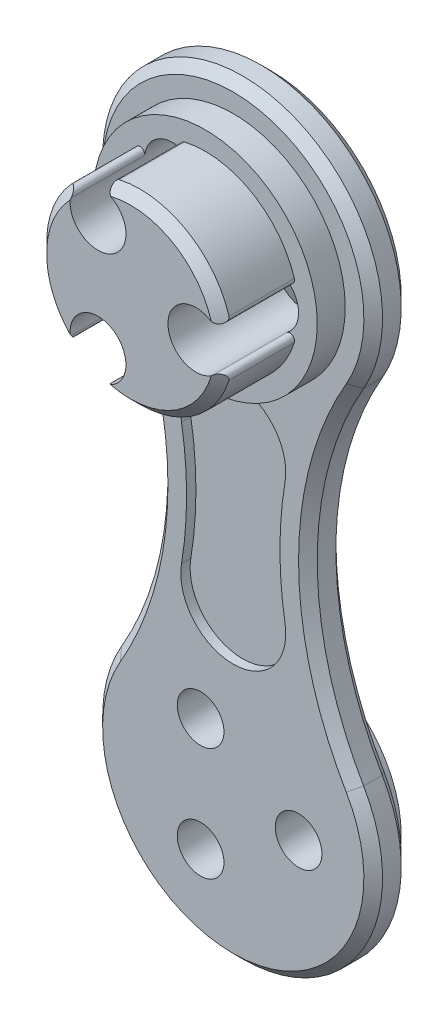
SolidWorks part; units mm, degrees
material "A2017"
ref_plane "正面" through (0, 0, 0) normal (0, 0, 1) x (1, 0, 0)
ref_plane "平面" through (0, 0, 0) normal (0, 1, 0) x (1, 0, 0)
ref_plane "右側面" through (0, 0, 0) normal (1, 0, 0) x (0, 0, -1)
sketch "ｽｹｯﾁ1" plane through (0, 0, 0) normal (0, 0, 1) x (1, 0, 0)
  line L0 (0, 12.9904) -> (0, 0) construction
  line L1 (0, 0) -> (0, -12.9904) construction
  line L2 (0, 0) -> (50000, 0) construction
  arc A0 (6.4848, 9.2225) -> (-6.4848, 9.2225) centre (0, 12.9904) ccw
  arc A1 (-6.4848, -9.2225) -> (6.4848, -9.2225) centre (0, -12.9904) ccw
  arc A2 (-6.4848, 9.2225) -> (-6.4848, -9.2225) centre (-22.3571, 0) cw
  arc A3 (6.4848, 9.2225) -> (6.4848, -9.2225) centre (22.3571, 0) ccw
  point P14 (-4, 0)
  point P15 (4, 0)
  dimension "D2" = 15
  dimension "D1" = 25.9808
  dimension "D3" = 8
extrude "ﾎﾞｽ - 押し出し1" add sketch "ｽｹｯﾁ1" along normal mid plane 2
sketch "ｽｹｯﾁ2" plane through (0, 0, 1) normal (0, 0, 1) x (1, 0, 0)
  circle A0 centre (0, 12.9904) radius 6
  dimension "D1" = 12
extrude "ﾎﾞｽ - 押し出し2" add sketch "ｽｹｯﾁ2" along normal blind 1.5
sketch "ｽｹｯﾁ3" plane through (0, 0, -1) normal (0, 0, -1) x (-1, 0, 0)
  circle A0 centre (0, -12.9904) radius 7.5
  arc A3 (-6.4848, -9.2225) -> (6.4848, -9.2225) centre (0, -12.9904) ccw construction
extrude "ﾎﾞｽ - 押し出し3" add sketch "ｽｹｯﾁ3" along normal blind 1
sketch "ｽｹｯﾁ4" plane through (0, 0, 2.5) normal (0, 0, 1) x (1, 0, 0)
  circle A0 centre (0, 12.9904) radius 5
  dimension "D1" = 10
extrude "ﾎﾞｽ - 押し出し4" add sketch "ｽｹｯﾁ4" along normal blind 4
sketch "ｽｹｯﾁ10" plane through (0, 0, 6.5) normal (0, 0, 1) x (1, 0, 0)
  line L0 (-1.75, 16.0215) -> (-3.75, 19.4856) construction
  line L1 (-4, 0) -> (4, 0) construction
  line L2 (-1.75, -16.0215) -> (-3.75, -19.4856) construction
  arc A0 (-3.241, 16.1857) -> (-1.1468, 17.3948) centre (-1.75, 16.0215) ccw
  circle A1 centre (0, 12.9904) radius 5 construction
  arc A2 (4.3878, 14.1995) -> (4.3878, 11.7813) centre (3.5, 12.9904) ccw
  arc A3 (-1.1468, 8.5859) -> (-3.241, 9.795) centre (-1.75, 9.9593) ccw
  arc A4 (6.4848, 9.2225) -> (-6.4848, 9.2225) centre (0, 12.9904) ccw construction
  circle A6 centre (0, 12.9904) radius 5 construction
  arc A7 (-3.241, 16.1857) -> (-3.6731, 16.3827) centre (-3.4895, 16.2131) ccw
  arc A9 (-1.1468, 17.3948) -> (-1.1013, 17.8676) centre (-1.0462, 17.6237) cw
  arc A10 (4.3878, 11.7813) -> (4.7744, 11.5055) centre (4.5357, 11.5798) cw
  arc A11 (4.3878, 14.1995) -> (4.7744, 14.4752) centre (4.5357, 14.401) ccw
  arc A12 (-3.241, 9.795) -> (-3.6731, 9.598) centre (-3.4895, 9.7676) cw
  arc A13 (-1.1468, 8.5859) -> (-1.1013, 8.1132) centre (-1.0462, 8.357) ccw
  arc A16 (-1.1013, 17.8676) -> (-3.6731, 16.3827) centre (0, 12.9904) ccw
  arc A17 (4.7744, 11.5055) -> (4.7744, 14.4752) centre (0, 12.9904) ccw
  arc A18 (-3.6731, 9.598) -> (-1.1013, 8.1132) centre (0, 12.9904) ccw
  arc A19 (-6.4848, -9.2225) -> (-6.4848, 9.2225) centre (-22.3571, 0) ccw construction
  arc A20 (6.4848, 9.2225) -> (6.4848, -9.2225) centre (22.3571, 0) ccw construction
  arc A21 (-3.6731, -9.598) -> (-1.1013, -8.1132) centre (0, -12.9904) cw
  arc A22 (4.7744, -11.5055) -> (4.7744, -14.4752) centre (0, -12.9904) cw
  arc A23 (-1.1013, -17.8676) -> (-3.6731, -16.3827) centre (0, -12.9904) cw
  arc A26 (-1.1468, -8.5859) -> (-1.1013, -8.1132) centre (-1.0462, -8.357) cw
  arc A27 (-3.241, -9.795) -> (-3.6731, -9.598) centre (-3.4895, -9.7676) ccw
  arc A28 (4.3878, -14.1995) -> (4.7744, -14.4752) centre (4.5357, -14.401) cw
  arc A29 (4.3878, -11.7813) -> (4.7744, -11.5055) centre (4.5357, -11.5798) ccw
  arc A30 (-1.1468, -17.3948) -> (-1.1013, -17.8676) centre (-1.0462, -17.6237) ccw
  arc A31 (-3.241, -16.1857) -> (-3.6731, -16.3827) centre (-3.4895, -16.2131) cw
  arc A34 (-1.1468, -8.5859) -> (-3.241, -9.795) centre (-1.75, -9.9593) cw
  arc A35 (4.3878, -14.1995) -> (4.3878, -11.7813) centre (3.5, -12.9904) cw
  arc A36 (-3.241, -16.1857) -> (-1.1468, -17.3948) centre (-1.75, -16.0215) cw
  point P13 (0, 12.9904)
  point P45 (0, 12.9904)
  dimension "D2" = 3
  dimension "D3" = 0.5
  dimension "D1" = 3
  dimension "D4" = 3
extrude "ｶｯﾄ - 押し出し2" cut sketch "ｽｹｯﾁ10" against normal through all
sketch "ｽｹｯﾁ13" plane through (0, 0, 2.5) normal (0, 0, 1) x (1, 0, 0)
  circle A0 centre (0, 12.9904) radius 6 construction
  circle A1 centre (0, 12.9904) radius 6
extrude "ﾎﾞｽ - 押し出し7" add sketch "ｽｹｯﾁ13" against normal up to surface (3.5 mm away) up to face at (-2.0452, 9.448, -1)
sketch "ｽｹｯﾁ14" plane through (0, 0, -2) normal (0, 0, -1) x (-1, 0, 0)
  arc A0 (6.4848, -9.2225) -> (-6.4848, -9.2225) centre (0, -12.9904) ccw construction
  circle A1 centre (0, -12.9904) radius 7.5
  arc A2 (1.1468, -8.5859) -> (3.241, -9.795) centre (1.75, -9.9593) ccw construction
  arc A4 (3.241, -16.1857) -> (1.1468, -17.3948) centre (1.75, -16.0215) ccw construction
  arc A5 (-4.3878, -14.1995) -> (-4.3878, -11.7813) centre (-3.5, -12.9904) ccw construction
  circle A6 centre (1.75, -9.9593) radius 1.5
  circle A8 centre (1.75, -16.0215) radius 1.5
  circle A9 centre (-3.5, -12.9904) radius 1.5
extrude "ﾎﾞｽ - 押し出し8" add sketch "ｽｹｯﾁ14" against normal up to surface (3 mm away) up to face at (-2.0452, -16.5328, 1)
sketch "ｽｹｯﾁ18" plane through (0, 0, 2.5) normal (0, 0, 1) x (1, 0, 0)
  arc A0 (4.3878, 14.1995) -> (4.3878, 11.7813) centre (3.5, 12.9904) ccw construction
  arc A1 (-3.241, 16.1857) -> (-1.1468, 17.3948) centre (-1.75, 16.0215) ccw construction
  arc A2 (-1.1468, 8.5859) -> (-3.241, 9.795) centre (-1.75, 9.9593) ccw construction
  circle A4 centre (3.5, 12.9904) radius 1.5
  circle A5 centre (-1.75, 16.0215) radius 1.5
  circle A6 centre (-1.75, 9.9593) radius 1.5
extrude "ｶｯﾄ - 押し出し3" cut sketch "ｽｹｯﾁ18" against normal through all
sketch "ｽｹｯﾁ19" plane through (0, 0, -2) normal (0, 0, -1) x (-1, 0, 0)
  circle A0 centre (1.75, -9.9593) radius 1
  circle A1 centre (1.75, -16.0215) radius 1
  circle A3 centre (-3.5, -12.9904) radius 1
  circle A4 centre (1.75, -9.9593) radius 1.5 construction
  circle A5 centre (1.75, -9.9593) radius 1.5
  circle A7 centre (1.75, -16.0215) radius 1.5 construction
  circle A8 centre (-3.5, -12.9904) radius 1.5 construction
  circle A10 centre (1.75, -16.0215) radius 1.5
  circle A11 centre (-3.5, -12.9904) radius 1.5
  dimension "D1" = 2
extrude "ﾎﾞｽ - 押し出し9" add sketch "ｽｹｯﾁ19" against normal up to surface (3 mm away)
hole_wizard "M3x0.5 ねじ穴1" positions "ｽｹｯﾁ21" profile "ｽｹｯﾁ20" tap size "M3x0.5" standard "Jis" end condition through all
sketch "ｽｹｯﾁ21" plane through (0, 0, 1) normal (0, 0, 1) x (1, 0, 0)
  point P0 (-1.75, -9.9593)
  point P6 (-1.75, -16.0215)
  point P9 (3.5, -12.9904)
sketch "ｽｹｯﾁ20" plane through (-1.75, -9.9593, 1) normal (1, 0, 0) x (0, -1, 0)
  line L0 (0, 0) -> (0, 3)
  line L1 (0, 3) -> (1.25, 3)
  line L2 (1.25, 3) -> (1.25, 0)
  line L5 (1.25, 0) -> (0, 0)
  line L11 (0, -6.35) -> (0, 107.95) construction
  dimension "次ｻｰﾌｪｽまでのねじ下穴ﾄﾞﾘﾙ直径" = 2.5
  dimension "次ｻｰﾌｪｽまでのねじ下穴ﾄﾞﾘﾙの深さ" = 3
cosmetic thread "穴のねじ山1" parameters "D2"=3
cosmetic thread "穴のねじ山2" parameters "D2"=3
cosmetic thread "穴のねじ山4" parameters "D2"=3
sketch "ｽｹｯﾁ22" plane through (0, 0, -2) normal (0, 0, -1) x (-1, 0, 0)
  circle A0 centre (0, -12.9904) radius 6
  circle A1 centre (0, -12.9904) radius 7.5 construction
  circle A2 centre (0, -12.9904) radius 7.5
  dimension "D1" = 12
extrude "ｶｯﾄ - 押し出し4" cut sketch "ｽｹｯﾁ22" against normal up to surface (1 mm away) up to face at (-3.25, 9.9593, -1)
chamfer "面取り1" distance 1.7 angle 45 3 edges at (-3.25, 16.0215, -1) (-3.25, 9.9593, -1) (2, 12.9904, -1)
chamfer "面取り2" distance 0.5 angle 45 19 edges at (4, 0, 1) (0, 20.4904, 1) (-5, 12.9904, 6.5) (-3.3858, 16.4406, 6.5) (-1.2951, 17.6477, 6.5) (-4, 0, 1) (0, 20.4904, -1) (2.5, 17.3205, 6.5) (4.6809, 14.1974, 6.5) (4.6809, 11.7833, 6.5) (2.5, 8.6603, 6.5) (0, -20.4904, 1) (-1.2951, 8.3331, 6.5) (-3.3858, 9.5402, 6.5)
sketch "ｽｹｯﾁ23" plane through (0, 0, 1) normal (0, 0, 1) x (1, 0, 0)
  arc A2 (5.1878, 9.976) -> (5.1878, -9.976) centre (22.3571, 0) ccw
  arc A3 (2.7736, 3.2848) -> (2.7736, -3.2848) centre (22.3571, 0) ccw
  arc A4 (2.7736, 3.2848) -> (-2.7736, 3.2848) centre (0, 3.75) ccw
  arc A5 (-5.1878, -9.976) -> (-5.1878, 9.976) centre (-22.3571, 0) ccw
  arc A6 (-2.7736, -3.2848) -> (-2.7736, 3.2848) centre (-22.3571, 0) ccw
  arc A7 (-2.7736, -3.2848) -> (2.7736, -3.2848) centre (0, -3.75) ccw
  dimension "D3" = 7.5
  dimension "D1" = 1.5
  dimension "D2" = 1.5
extrude "ｶｯﾄ - 押し出し5" cut sketch "ｽｹｯﾁ23" against normal blind 0.5
sketch "ｽｹｯﾁ24" plane through (0, 0, -1) normal (0, 0, -1) x (-1, 0, 0)
  arc A4 (-2.7736, -3.2848) -> (-2.7736, 3.2848) centre (-22.3571, 0) ccw
  arc A5 (-2.7736, -3.2848) -> (2.7736, -3.2848) centre (0, -3.75) ccw
  arc A6 (2.7736, 3.2848) -> (2.7736, -3.2848) centre (22.3571, 0) ccw
  arc A7 (2.7736, 3.2848) -> (-2.7736, 3.2848) centre (0, 3.75) ccw
  arc A8 (-2.7736, -3.2848) -> (-2.7736, 3.2848) centre (-22.3571, 0) ccw
  arc A9 (-2.7736, -3.2848) -> (2.7736, -3.2848) centre (0, -3.75) ccw
  arc A10 (2.7736, 3.2848) -> (2.7736, -3.2848) centre (22.3571, 0) ccw
  arc A11 (2.7736, 3.2848) -> (-2.7736, 3.2848) centre (0, 3.75) ccw
  dimension "D1" = 0
extrude "ｶｯﾄ - 押し出し6" cut sketch "ｽｹｯﾁ24" against normal blind 0.5
